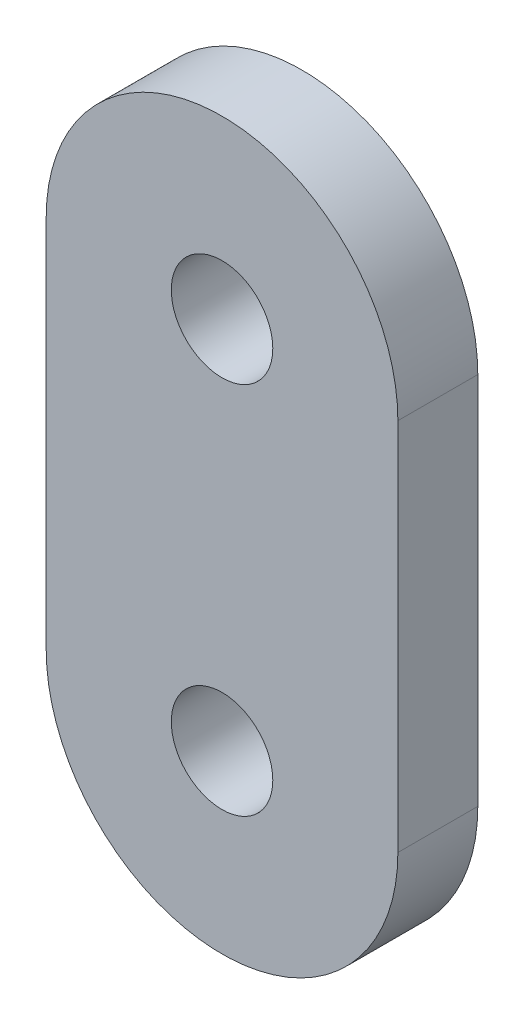
SolidWorks part; units mm, degrees
material "Plain Carbon Steel"
ref_plane "Front Plane" through (0, 0, 0) normal (0, 0, 1) x (1, 0, 0)
ref_plane "Top Plane" through (0, 0, 0) normal (0, 1, 0) x (1, 0, 0)
ref_plane "Right Plane" through (0, 0, 0) normal (1, 0, 0) x (0, 0, -1)
sketch "Sketch1" plane through (0, 0, 0) normal (0, 0, 1) x (1, 0, 0)
  line L0 (11, 0) -> (11, 23.393)
  line L1 (-11, 23.393) -> (-11, 0)
  arc A0 (-11, 0) -> (11, 0) centre (0, 0) ccw
  arc A1 (11, 23.393) -> (-11, 23.393) centre (0, 23.393) ccw
  circle A2 centre (0, 0) radius 3.175
  circle A3 centre (0, 23.393) radius 3.175
  dimension "D1" = 6.35
  dimension "D2" = 6.35
extrude "Boss-Extrude1" add sketch "Sketch1" along normal blind 5
